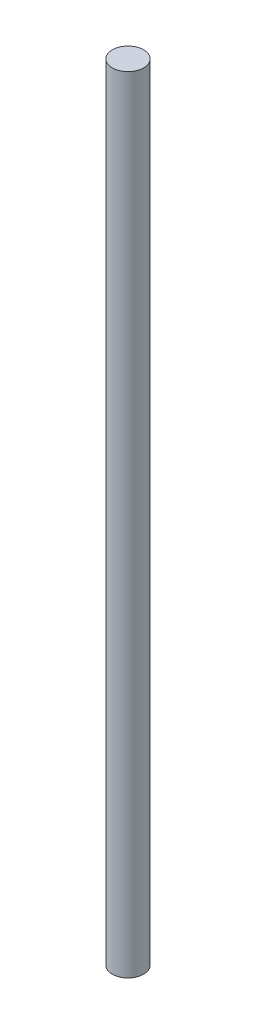
SolidWorks part; units mm, degrees
material "Stainless Steel (ferritic)"
ref_plane "Front Plane" through (0, 0, 0) normal (0, 0, 1) x (1, 0, 0)
ref_plane "Top Plane" through (0, 0, 0) normal (0, 1, 0) x (1, 0, 0)
ref_plane "Right Plane" through (0, 0, 0) normal (1, 0, 0) x (0, 0, -1)
sketch "Sketch1" plane through (0, 0, 0) normal (0, 1, 0) x (1, 0, 0)
  circle A0 centre (0, 0) radius 4
  dimension "D1" = 8
extrude "Boss-Extrude1" add sketch "Sketch1" along normal mid plane 200 contours A0
